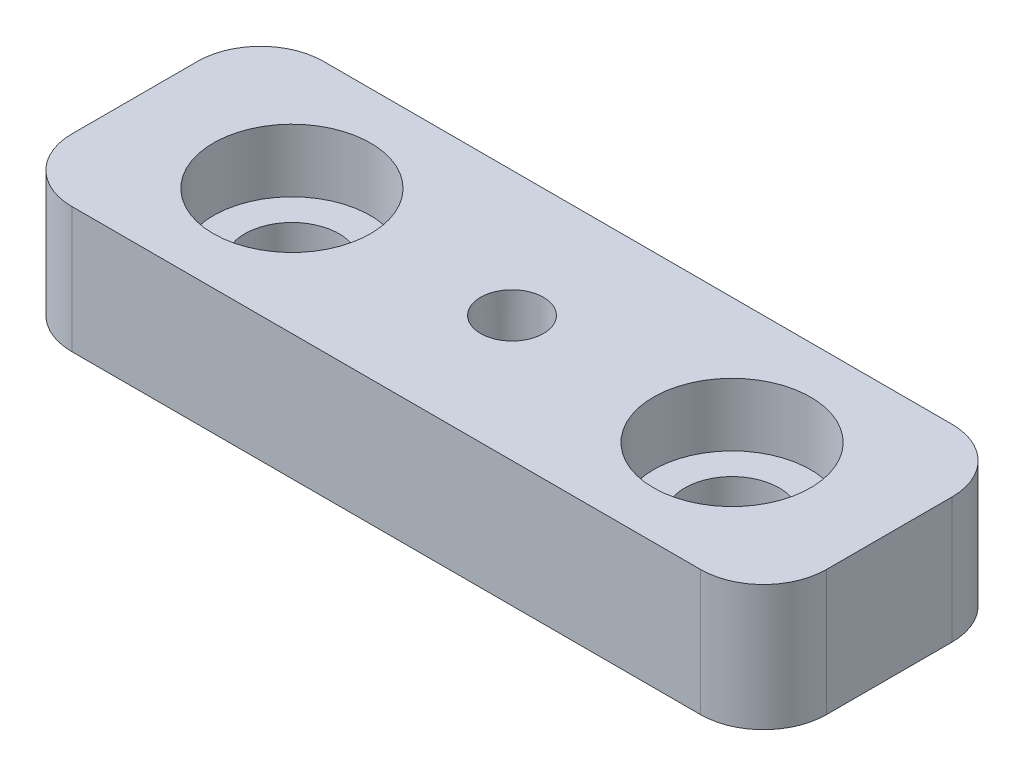
SolidWorks part; units mm, degrees
ref_plane "Front Plane" through (0, 0, 0) normal (0, 0, 1) x (1, 0, 0)
ref_plane "Top Plane" through (0, 0, 0) normal (0, 1, 0) x (1, 0, 0)
ref_plane "Right Plane" through (0, 0, 0) normal (1, 0, 0) x (0, 0, -1)
sketch "Sketch1" plane through (0, 0, 0) normal (0, 1, 0) x (1, 0, 0)
  line L0 (0, 4) -> (10, 4)
  line L1 (12, 2) -> (12, -2)
  line L2 (10, -4) -> (0, -4)
  line L3 (0, -4) -> (-10, -4)
  line L4 (-12, -2) -> (-12, 2)
  line L5 (-10, 4) -> (0, 4)
  line L6 (0, -55) -> (0, 55) construction
  circle A0 centre (0, 0) radius 4 construction
  circle A1 centre (0, 0) radius 1
  arc A2 (10, -4) -> (12, -2) centre (10, -2) ccw
  arc A3 (12, 2) -> (10, 4) centre (10, 2) ccw
  arc A4 (-10, -4) -> (-12, -2) centre (-10, -2) cw
  arc A5 (-10, 4) -> (-12, 2) centre (-10, 2) ccw
  circle A6 centre (0, 0) radius 2.5
  circle A7 centre (-7, 0) radius 1.5
  circle A8 centre (-7, 0) radius 2.5
  circle A9 centre (7, 0) radius 2.5
  circle A10 centre (7, 0) radius 1.5
  point P14 (12, 4)
  point P19 (-12, 4)
  dimension "D1" = 2
  dimension "D2" = 8
  dimension "D5" = 2
  dimension "D6" = 5
  dimension "D7" = 3
  dimension "D8" = 5
  dimension "D3" = 12
  dimension "D4" = 12
  dimension "D9" = 5
  dimension "D10" = 4
  dimension "D11" = 14
extrude "Boss-Extrude1" add sketch "Sketch1" along normal blind 4 contours L3 A4 L4 A5 L5 L0 A3 L1 A2 L2
extrude "Cut-Extrude1" cut sketch "Sketch1<3>" along normal up to next contours A1 | A7 | A10
sketch "Sketch1<3>" plane through (0, 0, 0) normal (0, 1, 0) x (1, 0, 0) same geometry as "Sketch1"
extrude "Cut-Extrude2" cut sketch "Sketch1<4>" along normal blind 2 contours A6
sketch "Sketch1<4>" plane through (0, 0, 0) normal (0, 1, 0) x (1, 0, 0) same geometry as "Sketch1"
ref_plane "Plane1" through (0, 4, 0) normal (0, 1, 0) x (1, 0, 0)
sketch "Sketch2" plane through (0, 4, 0) normal (0, 1, 0) x (1, 0, 0)
  circle A0 centre (-7, 0) radius 2.5
  circle A1 centre (7, 0) radius 2.5
  dimension "D1" = 5
  dimension "D2" = 5
extrude "Cut-Extrude3" cut sketch "Sketch2" against normal blind 2
